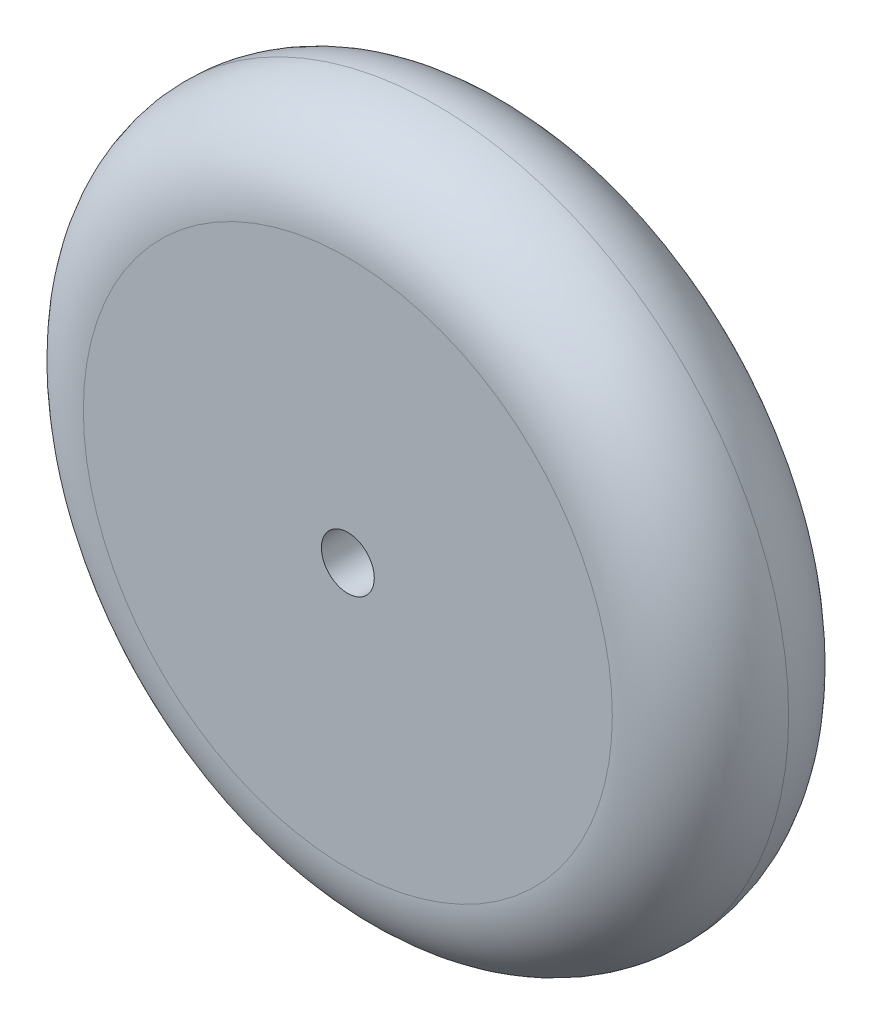
SolidWorks part; units mm, degrees
ref_plane "Front Plane" through (0, 0, 0) normal (0, 0, 1) x (1, 0, 0)
ref_plane "Top Plane" through (0, 0, 0) normal (0, 1, 0) x (1, 0, 0)
ref_plane "Right Plane" through (0, 0, 0) normal (1, 0, 0) x (0, 0, -1)
sketch "Sketch1" plane through (0, 0, 0) normal (0, 0, 1) x (1, 0, 0)
  circle A0 centre (0, 0) radius 20
  dimension "D1" = 40
extrude "Boss-Extrude1" add sketch "Sketch1" along normal blind 10
fillet "Fillet1" radius 5 1 edges at (20, 0, 10)
fillet "Fillet2" radius 5 1 edges at (20, 0, 0)
sketch "Sketch2" plane through (0, 0, 10) normal (0, 0, 1) x (1, 0, 0)
  circle A0 centre (0, 0) radius 1.5
  dimension "D1" = 3
extrude "Cut-Extrude1" cut sketch "Sketch2" against normal through all
